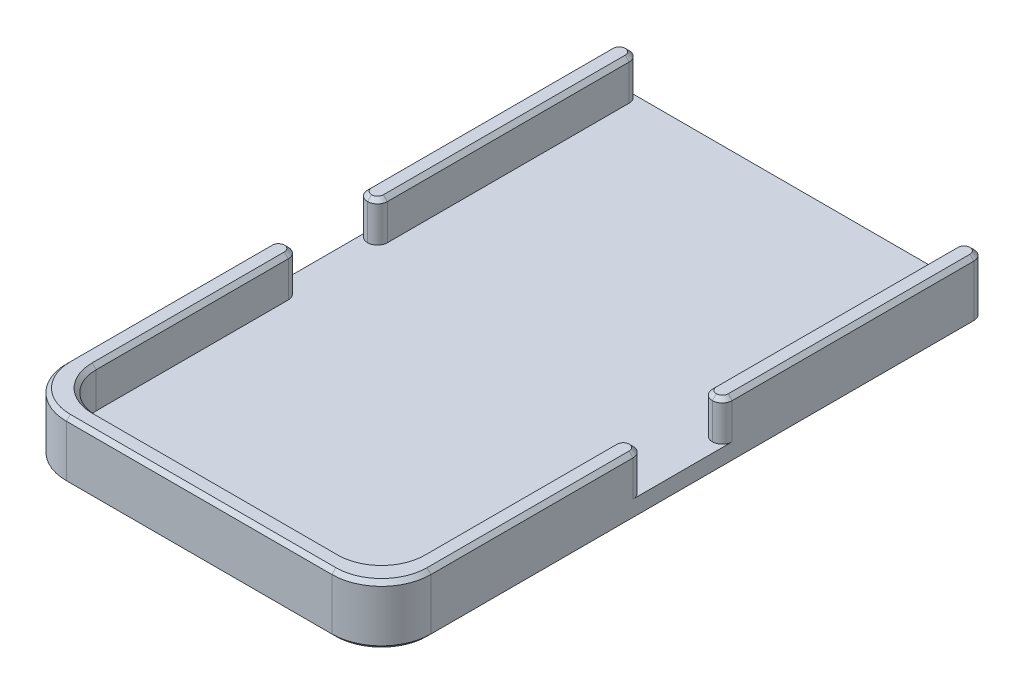
SolidWorks part; units mm, degrees
ref_plane "Front Plane" through (0, 0, 0) normal (0, 0, 1) x (1, 0, 0)
ref_plane "Top Plane" through (0, 0, 0) normal (0, 1, 0) x (1, 0, 0)
ref_plane "Right Plane" through (0, 0, 0) normal (1, 0, 0) x (0, 0, -1)
sketch "Sketch1" plane through (0, 0, 0) normal (0, 1, 0) x (1, 0, 0)
  line L0 (-29.21, -48.26) -> (-29.21, 48.26)
  line L1 (-26.035, -45.085) -> (26.035, -45.085)
  line L2 (-26.035, -45.085) -> (-26.035, 45.085)
  line L3 (-26.035, 45.085) -> (26.035, 45.085)
  line L4 (26.035, -45.085) -> (26.035, 45.085)
  line L5 (-26.035, -45.085) -> (26.035, 45.085) construction
  line L6 (-26.035, 45.085) -> (26.035, -45.085) construction
  line L7 (-29.21, 48.26) -> (29.21, 48.26)
  line L8 (29.21, -48.26) -> (29.21, 48.26)
  line L9 (-29.21, -48.26) -> (29.21, -48.26)
  point P0 (0, 0)
  dimension "D1" = 52.07
  dimension "D2" = 90.17
  dimension "D3" = 3.175
  dimension "D4" = 3.175
  dimension "D5" = 3.175
  dimension "D6" = 3.175
extrude "Boss-Extrude1" add sketch "Sketch1" along normal blind 6.35
extrude "Boss-Extrude2" add sketch "Sketch1<4>" against normal blind 3.175 contours L9 L8 L7 L0
sketch "Sketch1<4>" plane through (0, 0, 0) normal (0, 1, 0) x (1, 0, 0) same geometry as "Sketch1"
fillet "Fillet1" radius 6.35 4 edges at (26.035, 3.175, -45.085) (26.035, 3.175, 45.085) (-26.035, 3.175, 45.085) (-26.035, 3.175, -45.085)
sketch "Sketch4" plane through (0, 6.35, 0) normal (0, 1, 0) x (1, 0, 0)
  line L0 (26.035, -38.735) -> (26.035, 38.735) construction
  line L1 (-26.035, 53.5073) -> (26.035, 53.5073)
  line L2 (-26.035, 53.5073) -> (-26.035, 33.2818)
  line L3 (-26.035, 33.2818) -> (26.035, 33.2818)
  line L4 (26.035, 53.5073) -> (26.035, 33.2818)
  line L5 (-26.035, 53.5073) -> (26.035, 33.2818) construction
  line L6 (-26.035, 33.2818) -> (26.035, 53.5073) construction
  line L7 (-26.035, 38.735) -> (-26.035, -38.735) construction
  point P0 (0, 43.3945)
  point P5 (0, 0)
extrude "Cut-Extrude2" cut sketch "Sketch4" against normal up to surface (6.35 mm away) up to face at (0, 0, 0)
sketch "Sketch5" plane through (0, 6.35, 0) normal (0, 1, 0) x (1, 0, 0)
  line L1 (-39.4554, 6.35) -> (39.4554, 6.35)
  line L2 (-39.4554, 6.35) -> (-39.4554, -6.35)
  line L3 (-39.4554, -6.35) -> (39.4554, -6.35)
  line L4 (39.4554, 6.35) -> (39.4554, -6.35)
  line L5 (-39.4554, 6.35) -> (39.4554, -6.35) construction
  line L6 (-39.4554, -6.35) -> (39.4554, 6.35) construction
  point P0 (0, 0)
  dimension "D1" = 12.7
extrude "Cut-Extrude3" cut sketch "Sketch5" against normal up to surface (6.35 mm away) up to face at (0, 0, 12.2917)
fillet "Fillet2" radius 1.5875 12 edges at (-26.035, 3.175, -48.26) (26.035, 3.175, -48.26) (29.21, 1.5875, -48.26) (-29.21, 1.5875, -48.26) (29.21, 3.175, 6.35) (26.035, 3.175, 6.35) (29.21, 3.175, -6.35) (26.035, 3.175, -6.35) (-26.035, 3.175, 6.35) (-29.21, 3.175, 6.35) (-26.035, 3.175, -6.35) (-29.21, 3.175, -6.35)
fillet "Fillet3" radius 7.9375 2 edges at (29.21, 1.5875, 48.26) (-29.21, 1.5875, 48.26)
chamfer "Chamfer2" distance 0.635 angle 45 34 edges at (26.5, 6.35, -47.795) (26.035, 6.35, 23.3362) (24.1751, 6.35, 43.2251) (0, 6.35, 45.085) (-24.1751, 6.35, 43.2251) (-26.5, 6.35, -47.795) (0, 6.35, 48.26) (-28.745, 6.35, -47.795) (28.745, 6.35, -47.795) (-26.035, 6.35, 23.3362) (29.21, 6.35, -27.305) (-29.21, 6.35, -27.305) (28.745, 6.35, -6.815) (26.5, 6.35, -6.815) (-26.5, 6.35, -6.815) (-28.745, 6.35, -6.815) (-28.745, 6.35, 6.815) (-26.5, 6.35, 6.815) (26.5, 6.35, 6.815) (28.745, 6.35, 6.815) (26.035, 6.35, -27.305) (-26.035, 6.35, -27.305) (-26.8852, 6.35, 45.9352) (-29.21, 6.35, 24.13) (29.21, 6.35, 24.13) (26.8852, 6.35, 45.9352) (28.745, -3.175, -47.795) (0, -3.175, -48.26) (-28.745, -3.175, -47.795) (-29.21, -3.175, -3.175) (-26.8852, -3.175, 45.9352) (0, -3.175, 48.26) (26.8852, -3.175, 45.9352) (29.21, -3.175, -3.175)
